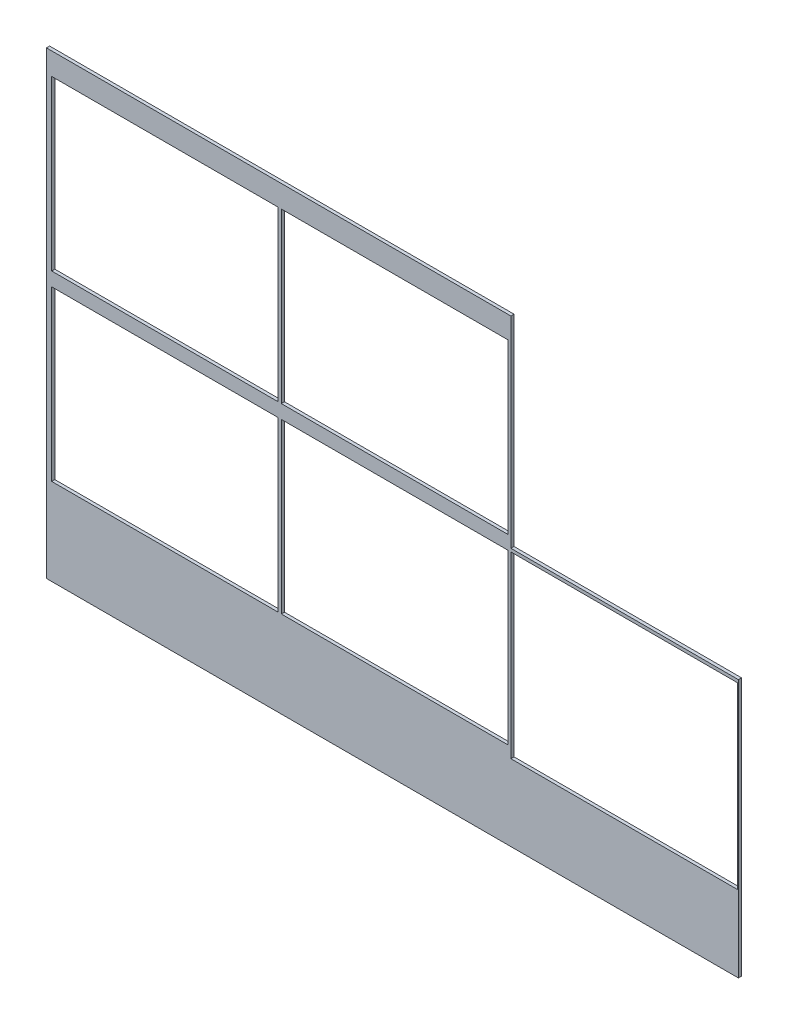
SolidWorks part; units mm, degrees
ref_plane "Спереди" through (0, 0, 0) normal (0, 0, 1) x (1, 0, 0)
ref_plane "Сверху" through (0, 0, 0) normal (0, 1, 0) x (1, 0, 0)
ref_plane "Справа" through (0, 0, 0) normal (1, 0, 0) x (0, 0, -1)
sketch "Эскиз1" plane through (0, 0, 0) normal (0, 0, 1) x (1, 0, 0)
  line L2 (-431, -436.3) -> (-431, 436.3)
  line L3 (-431, 436.3) -> (451, 436.3)
  line L4 (451, 54.3) -> (451, 436.3)
  line L6 (451, -430.3) -> (451, 436.3) construction
  line L8 (883, -436.3) -> (883, 54.3)
  line L9 (883, 54.3) -> (451, 54.3)
  line L11 (-431, -436.3) -> (883, -436.3)
  line L13 (-431, 54.3) -> (883, 54.3) construction
  line L14 (-431, -436.3) -> (883, -436.3) construction
  line L15 (-431, -436.3) -> (-431, 436.3) construction
  line L17 (-431, 436.3) -> (447, 436.3) construction
  point P3 (455, 116.285)
  point P4 (-589.555, -490.285)
  point P13 (451, 54.3)
  point P20 (0, 0)
extrude "Бобышка-Вытянуть1" add sketch "Эскиз1" against normal blind 6
sketch "Эскиз2" plane through (0, 0, -6) normal (0, 0, -1) x (-1, 0, 0)
  line L1 (-15, 394.3) -> (-445, 394.3)
  line L2 (-15, 394.3) -> (-15, 74.3)
  line L3 (-15, 74.3) -> (-445, 74.3)
  line L4 (-445, 394.3) -> (-445, 74.3)
  line L10 (-451, 54.3) -> (-451, 436.3) construction
  line L11 (-943, 394.3) -> (441, 394.3) construction
  dimension "D2" = 320
  dimension "D1" = 430
  dimension "D3" = 6
extrude "Вырез-Вытянуть1" cut sketch "Эскиз2" against normal through all
pattern_linear "Линейный массив1" count 2 spacing 436 along (-1, 0, 0) count 2 spacing 346 along (0, -1, 0) of "Вырез-Вытянуть1"
sketch "Эскиз3" plane through (0, 0, 0) normal (0, 0, 1) x (1, 0, 0)
  line L0 (445, 48.3) -> (445, -271.7) construction
  line L1 (451, 48.3) -> (881, 48.3)
  line L2 (451, 48.3) -> (451, -291.7)
  line L3 (451, -291.7) -> (881, -291.7)
  line L4 (881, 48.3) -> (881, -291.7)
  line L5 (15, 48.3) -> (445, 48.3) construction
  dimension "D1" = 430
  dimension "D3" = 6
  dimension "D2" = 340
extrude "Вырез-Вытянуть2" cut sketch "Эскиз3" against normal through all
equation "\"Ширина груза\"= 420"
equation "\"Глубина груза\"= 490"
equation "\"Высота груза\"= 297"
equation "\"Ширина ячейки\"= \"Ширина груза\" + 10"
equation "\"Глубина ячейки\"= \"Глубина груза\" + 10"
equation "\"Высота ячейки\"= \"Высота груза\" + 10 + 13"
equation "\"Колво ячеек ширина\"= 2"
equation "\"Колво ячеек высота\"= 2"
equation "\"Толщина стенки\" = 6"
equation "\"Крепление дверцы\"= 5"
equation "\"Ширина рейки\"= \"Толщина шестерни\""
equation "\"Высота рейки\"= 20"
equation "\"Высота пола\"= 20"
equation "\"Колво полозьев\"= 5"
equation "\"Отступ рейки\"= 20"
equation "\"Глубина каретки\"= \"Глубина ячейки\" + 30 + \"Мотор Y высота корпуса\" + 20"
equation "\"Длинна рейки\"= ( \"Ширина ячейки\" + \"Толщина стенки\" + \"Крепление дверцы\" ) * \"Колво ячеек ширина\" + \"Ширина ячейки выгрузки\" * \"Колво выгрузки\" + \"Толщина стенки\""
equation "\"Отступ шпильки\"= 26"
equation "\"Диаметр шпильки\"= 5"
equation "\"Длинна шпильки\"= ( \"Высота ячейки\" + \"Толщина стенки\" + \"Высота пола\" ) * \"Колво ячеек высота\" + ( \"Толщина стенки\" + \"Отступ рейки\" ) * 2 "
equation "\"Ширина пластины\"= 50  "
equation "\"Высота зона выгрузки\"= \"Высота ячейки\" * 2 + \"Толщина стенки\" * 2"
equation "\"Колво выгрузки\"= 1"
equation "\"Ширина ячейки выгрузки\"= \"Ширина ячейки\" + \"Толщина стенки\" + \"Отступ крепления мотора фиксации\"*2"
equation "\"Отступ крепления мотора фиксации\" = 30"
equation "\"Мотор X ширина корпуса\"= 42.3"
equation "\"Мотор X высота корпуса\"= 42.3"
equation "\"Мотор X длина корпуса\"= 40"
equation "\"Мотор X вылет вала\"= 19.8"
equation "\"Мотор Y ширина корпуса\"= 42.3"
equation "\"Мотор Y высота корпуса\"= 42.3"
equation "\"Мотор Y длина корпуса\"= 48"
equation "\"Мотор Y вылет вала\"= 30"
equation "\"Мотор Z ширина корпуса\"= 42"
equation "\"Мотор Z высота корпуса\"= 42"
equation "\"Мотор Z длина корпуса\"= 40"
equation "\"Мотор Z вылет вала\"= 23"
equation "\"Мотор диаметр вала ПРЕДВ\"= 5"
equation "\"Мотор шаг крепления ПРЕДВ\"= 31"
equation "\"Мотор диаметр отверстий ПРЕДВ\"= 3"
equation "\"Мотор глубина отверстий ПРЕДВ\"= 4.5"
equation "\"Мотор диаметр буртика ПРЕДВ\"= 22"
equation "\"Мотор высота буртика ПРЕДВ\"= 2"
equation "\"Мотор диаметр шкива ПРЕДВ\"= 16"
equation "\"Мотор длина шкива ПРЕДВ\"= 12"
equation "\"Мотор отступ шкива ПРЕДВ\"= 5"
equation "\"Мотор X шаг градусов\"= 1.8"
equation "\"Мотор Y шаг градусов\"= 1.8"
equation "\"Мотор Z шаг градусов\"= 1.8"
equation "\"Мотор Y диаметр ротора\"= 25.78"
equation "\"Толщина шестерни\"= 10"
equation "\"D1@Бобышка-Вытянуть1\"=\"Толщина стенки\""
equation "\"D1@Линейный массив1\"=\"Колво ячеек ширина\""
equation "\"D2@Линейный массив1\"=\"Колво ячеек высота\""
equation "\"D3@Линейный массив1\"=\"Ширина ячейки\"+\"Толщина стенки\""
equation "\"D4@Линейный массив1\"=\"Высота ячейки\" + \"Высота пола\"+\"Толщина стенки\""
equation "\"D1@Эскиз2\"=\"Ширина ячейки\""
equation "\"D3@Эскиз2\"=\"Толщина стенки\""
equation "\"D1@Эскиз3\"=\"Ширина ячейки\""
equation "\"D2@Эскиз3\"=\"Высота ячейки\" + \"Высота пола\""
equation "\"D3@Эскиз3\"=\"Толщина стенки\""
